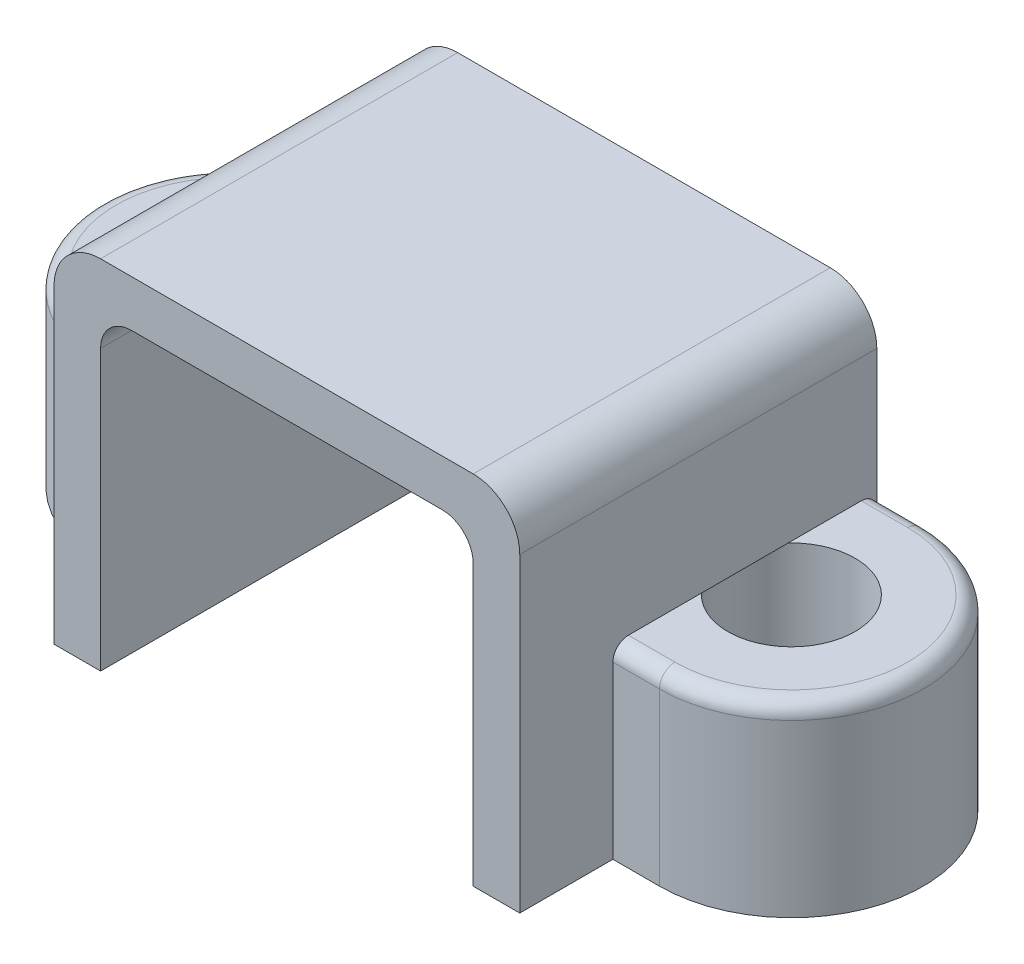
SolidWorks part; units mm, degrees
material "Custom Plastic"
ref_plane "Front Plane" through (0, 0, 0) normal (0, 0, 1) x (1, 0, 0)
ref_plane "Top Plane" through (0, 0, 0) normal (0, 1, 0) x (1, 0, 0)
ref_plane "Right Plane" through (0, 0, 0) normal (1, 0, 0) x (0, 0, -1)
sketch "Sketch1" plane through (0, 0, 0) normal (0, 0, 1) x (1, 0, 0)
  line L0 (0, -210.3757) -> (0, 10308.4069) construction
  line L1 (0, 0) -> (6, 0)
  line L2 (6, 0) -> (6, -10)
  line L3 (0, 1.5) -> (7.5, 1.5)
  line L4 (7.5, 1.5) -> (7.5, -10)
  line L5 (7.5, -10) -> (6, -10)
  line L6 (-7.5, -10) -> (-6, -10)
  line L7 (-7.5, 1.5) -> (-7.5, -10)
  line L8 (0, 1.5) -> (-7.5, 1.5)
  line L9 (-6, 0) -> (-6, -10)
  line L10 (0, 0) -> (-6, 0)
  dimension "D1" = 12
  dimension "D2" = 10
  dimension "D3" = 1.5
extrude "Boss-Extrude1" add sketch "Sketch1" along normal blind 11.5
sketch "Sketch3" plane through (0, -10, 0) normal (0, -1, 0) x (1, 0, 0)
  line L0 (0, -1000) -> (0, 49000) construction
  line L1 (7.5, 0) -> (-7.5, 0) construction
  line L2 (7.5, 0) -> (7.5, 8.5)
  line L3 (7.5, 11.5) -> (7.5, 0) construction
  line L4 (7.5, 0) -> (9, 0)
  line L5 (7.5, 8.5) -> (9, 8.5)
  line L6 (-7.5, 8.5) -> (-9, 8.5)
  line L7 (-7.5, 0) -> (-9, 0)
  line L8 (-7.5, 0) -> (-7.5, 8.5)
  arc A0 (9, 0) -> (9, 8.5) centre (9, 4.25) ccw
  arc A1 (-9, 0) -> (-9, 8.5) centre (-9, 4.25) cw
  point P5 (0, 0)
  point P10 (7.5, 4.25)
  point P22 (-7.5, 4.25)
  dimension "D1" = 8.5
  dimension "D2" = 1.5
extrude "Boss-Extrude2" add sketch "Sketch3" against normal blind 6
sketch "Sketch4" plane through (0, -10, 0) normal (0, -1, 0) x (1, 0, 0)
  line L1 (0, -1000) -> (0, 49000) construction
  circle A0 centre (-9, 4.25) radius 2.05
  arc A1 (-9, 8.5) -> (-9, 0) centre (-9, 4.25) ccw construction
  circle A2 centre (9, 4.25) radius 2.05
  dimension "D1" = 4.1
extrude "Cut-Extrude1" cut sketch "Sketch4" against normal up to surface (6 mm away) up to face at (9.3125, -4, 4.25)
fillet "Fillet1" radius 1.5 2 edges at (-7.5, 1.5, 5.75) (7.5, 1.5, 5.75)
fillet "Fillet2" radius 0.5 6 edges at (8.25, -4, 0) (8.25, -4, 8.5) (13.25, -4, 4.25) (-8.25, -4, 8.5) (-8.25, -4, 0) (-13.25, -4, 4.25)
fillet "Fillet3" radius 1 2 edges at (-6, 0, 5.75) (6, 0, 5.75)
equation "\"Hole_Diameter\"= 4.1mm"
equation "\"Hole_Depth\" = 6mm"
equation "\"D1@Sketch4\"=\"Hole_Diameter\""
equation "\"D1@Boss-Extrude2\"=\"Hole_Depth\""
